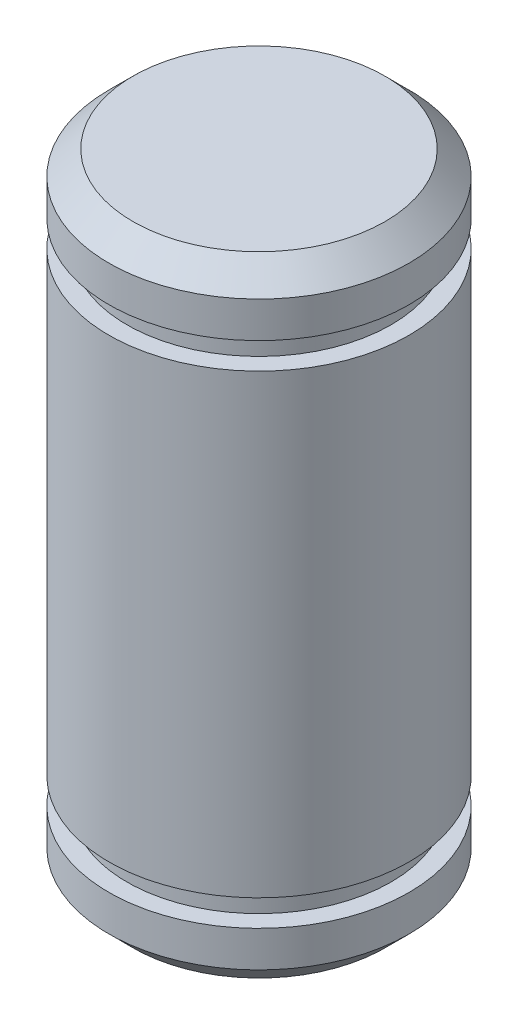
SolidWorks part; units mm, degrees
ref_plane "Front" through (0, 0, 0) normal (0, 0, 1) x (1, 0, 0)
ref_plane "Top" through (0, 0, 0) normal (0, 1, 0) x (1, 0, 0)
ref_plane "Right" through (0, 0, 0) normal (1, 0, 0) x (0, 0, -1)
ref_axis "side-side" through (80.9, 0, 0) along (-1, 0, 0)
ref_axis "up-down" through (0, 50, 0) along (0, -1, 0)
ref_axis "front-back" through (0, 0, -80.9) along (0, 0, 1)
sketch "Sketch1" plane through (0, 0, 0) normal (0, 0, 1) x (1, 0, 0)
  line L0 (-3.175, 4.826) -> (-3.175, -4.826)
  line L1 (0, 6.6548) -> (-3.175, 6.6548)
  line L2 (0, 6.6548) -> (0, -6.6548)
  line L3 (0, -6.6548) -> (-3.175, -6.6548)
  line L4 (-3.175, 6.6548) -> (-3.175, 5.3848)
  line L5 (-3.175, 5.3848) -> (-2.794, 5.3848)
  line L6 (-3.175, -5.3848) -> (-3.175, -6.6548)
  line L7 (-3.175, 4.826) -> (-2.794, 4.826)
  line L8 (-2.794, 5.3848) -> (-2.794, 4.826)
  line L9 (-3.175, -4.826) -> (-2.794, -4.826)
  line L10 (0, 6.6548) -> (0, 13.3378) construction
  line L11 (-3.175, -5.3848) -> (-2.794, -5.3848)
  line L12 (-2.794, -4.826) -> (-2.794, -5.3848)
  dimension "D1" = 6.35
  dimension "D2" = 0.5588
  dimension "D3" = 1.27
  dimension "D4" = 9.652
  dimension "D5" = 0.381
revolve "Revolve1" add sketch "Sketch1" angle 360 about L10
chamfer "Chamfer1" distance 0.508 angle 45 2 edges at (3.175, -6.6548, 0) (3.175, 6.6548, 0)
